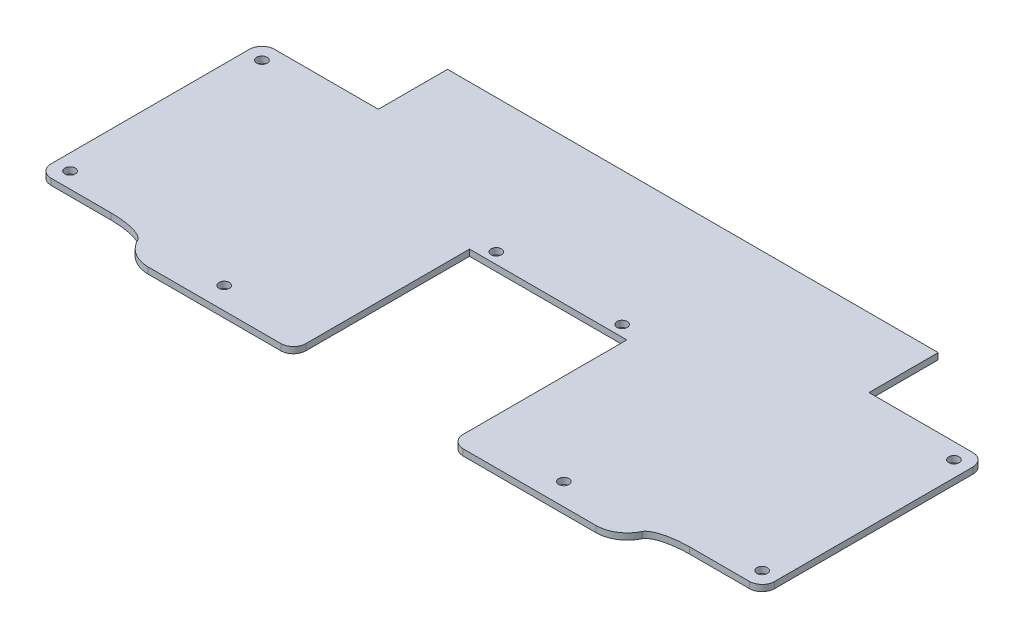
SolidWorks part; units mm, degrees
material "ABS PC"
ref_plane "Front Plane" through (0, 0, 0) normal (0, 0, 1) x (1, 0, 0)
ref_plane "Top Plane" through (0, 0, 0) normal (0, 1, 0) x (1, 0, 0)
ref_plane "Right Plane" through (0, 0, 0) normal (1, 0, 0) x (0, 0, -1)
sketch "Sketch1" plane through (0, 0, 0) normal (0, 1, 0) x (1, 0, 0)
  line L1 (0, 0) -> (230, 0)
  line L2 (0, 0) -> (0, 102)
  line L3 (0, 102) -> (230, 102)
  line L4 (230, 0) -> (230, 102)
  dimension "D1" = 230
  dimension "D2" = 102
extrude "Boss-Extrude1" add sketch "Sketch1" along normal blind 2
sketch "Sketch2" plane through (0, 2, 0) normal (0, 1, 0) x (1, 0, 0)
  line L1 (0, 102) -> (37, 102)
  line L2 (0, 102) -> (0, 80)
  line L3 (0, 80) -> (37, 80)
  line L4 (37, 102) -> (37, 80)
  line L5 (0, 0) -> (35, 0)
  line L6 (0, 0) -> (0, 9)
  line L7 (0, 9) -> (35, 9)
  line L8 (35, 0) -> (35, 9)
  line L9 (230, 102) -> (193, 102)
  line L10 (230, 102) -> (230, 80)
  line L11 (230, 80) -> (193, 80)
  line L12 (193, 102) -> (193, 80)
  line L13 (230, 0) -> (195, 0)
  line L14 (230, 0) -> (230, 9)
  line L15 (230, 9) -> (195, 9)
  line L16 (195, 0) -> (195, 9)
  line L17 (90, 0) -> (140, 0)
  line L18 (90, 0) -> (90, 56)
  line L19 (90, 56) -> (140, 56)
  line L20 (140, 0) -> (140, 56)
  dimension "D1" = 37
  dimension "D2" = 22
  dimension "D3" = 9
  dimension "D4" = 37
  dimension "D5" = 35
  dimension "D6" = 35
  dimension "D7" = 9
  dimension "D8" = 22
  dimension "D9" = 90
  dimension "D10" = 90
  dimension "D11" = 56
extrude "Cut-Extrude1" cut sketch "Sketch2" against normal through all
sketch "Sketch3" plane through (0, 0, 0) normal (0, -1, 0) x (1, 0, 0)
  line L0 (35, -9) -> (0, -9) construction
  line L1 (0, -80) -> (0, -9) construction
  line L2 (0, -80) -> (37, -80) construction
  line L3 (115, -56) -> (115, -102) construction
  line L4 (193, -102) -> (37, -102) construction
  line L6 (90, -56) -> (90, 0) construction
  line L8 (140, -56) -> (90, -56) construction
  line L9 (140, 0) -> (140, -56) construction
  circle A0 centre (5, -14) radius 1.65
  circle A1 centre (5, -75) radius 1.65
  circle A10 centre (95, -59.5) radius 1.65
  circle A11 centre (135, -59.5) radius 1.65
  circle A12 centre (225, -14) radius 1.65
  circle A13 centre (225, -75) radius 1.65
  dimension "D1" = 3.3
  dimension "D6" = 3.3
  dimension "D7" = 5
  dimension "D11" = 5
  dimension "D8" = 3.3
  dimension "D10" = 3.3
  dimension "D2" = 5
  dimension "D3" = 5
  dimension "D4" = 5
  dimension "D5" = 5
  dimension "D9" = 3.5
  dimension "D12" = 3.5
extrude "Cut-Extrude2" cut sketch "Sketch3" against normal blind 10
fillet "Fillet1" radius 4 6 edges at (90, 1, 0) (140, 1, 0) (230, 1, -9) (230, 1, -80) (0, 1, -9) (0, 1, -80)
fillet "Fillet2" radius 4 2 edges at (195, 1, -9) (35, 1, -9)
fillet "Fillet3" radius 10 2 edges at (35, 1, 0) (195, 1, 0)
sketch "Sketch4" plane through (0, 0, 0) normal (0, -1, 0) x (1, 0, 0)
  line L0 (0, -76) -> (0, -13) construction
  line L1 (115, -102) -> (115, -56) construction
  line L2 (193, -102) -> (37, -102) construction
  line L3 (140, -56) -> (90, -56) construction
  circle A0 centre (61, -7) radius 1.65
  circle A1 centre (5, -14) radius 1.65 construction
  circle A2 centre (169, -7) radius 1.65
  dimension "D2" = 3.3
  dimension "D1" = 61
  dimension "D3" = 7
extrude "Cut-Extrude3" cut sketch "Sketch4" against normal blind 10
